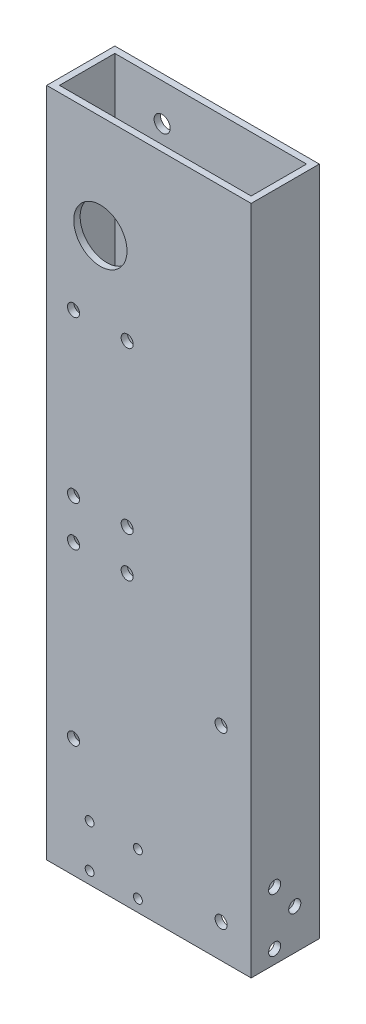
SolidWorks part; units mm, degrees
material "6063-T5"
ref_plane "Front Plane" through (0, 0, 0) normal (0, 0, 1) x (1, 0, 0)
ref_plane "Top Plane" through (0, 0, 0) normal (0, 1, 0) x (1, 0, 0)
ref_plane "Right Plane" through (0, 0, 0) normal (1, 0, 0) x (0, 0, -1)
sketch "Sketch1" plane through (0, 0, 0) normal (0, 1, 0) x (1, 0, 0)
  line L1 (-76.2, 25.4) -> (76.2, 25.4)
  line L2 (-76.2, 25.4) -> (-76.2, -25.4)
  line L3 (-76.2, -25.4) -> (76.2, -25.4)
  line L4 (76.2, 25.4) -> (76.2, -25.4)
  line L5 (-76.2, 25.4) -> (76.2, -25.4) construction
  line L6 (-76.2, -25.4) -> (76.2, 25.4) construction
  point P0 (0, 0)
  dimension "D1" = 152.4
  dimension "D2" = 50.8
extrude "Extrude-Thin1" add sketch "Sketch1" along normal blind 500 thin thin type one direction reverse wall 4.7625
hole_wizard "M8 Clearance Hole1" positions "Sketch3" profile "Sketch4" hole size "M8" standard "ANSI Metric" end condition through all
sketch "Sketch3" plane through (0, 0, 25.4) normal (0, 0, 1) x (1, 0, 0)
  line L0 (-76.2, 225) -> (3.8, 225)
  line L1 (-76.2, 500) -> (-76.2, 0) construction
  line L3 (-76.2, 0) -> (76.2, 0) construction
  line L4 (3.8, 225) -> (3.8, 385)
  line L5 (3.8, 385) -> (-76.2, 385)
  line L6 (-76.2, 385) -> (-76.2, 225)
  line L8 (-56.2, 215) -> (-16.2, 215)
  line L11 (-56.2, 215) -> (-56.2, 151.6667)
  line L12 (-56.2, 151.6667) -> (-56.2, 88.3333)
  line L13 (-56.2, 88.3333) -> (-56.2, 25)
  line L15 (-36.2, 215) -> (-36.2, 225)
  line L17 (-56.2, 25) -> (53.8, 25)
  line L18 (53.8, 25) -> (53.8, 151.6667)
  line L19 (53.8, 151.6667) -> (-56.2, 151.6667)
  line L22 (-56.2, 88.3333) -> (-76.2, 88.3333)
  line L27 (-36.2, 423) -> (-36.2, 385)
  circle A0 centre (-36.2, 423) radius 49.2125
  point P18 (-56.2, 215)
  point P19 (-16.2, 215)
  point P26 (-56.2, 88.3333)
  point P35 (53.8, 25)
  point P36 (53.8, 151.6667)
  dimension "D9" = 98.425
  dimension "D1" = 200
  dimension "D2" = 80
  dimension "D3" = 160
  dimension "D4" = 25
  dimension "D5" = 10
  dimension "D6" = 40
  dimension "D7" = 110
  dimension "D8" = 38
sketch "Sketch4" plane through (53.8, 151.6667, 25.4) normal (1, 0, 0) x (0, -1, 0)
  line L0 (0, 0) -> (0, 50.8)
  line L1 (0, 50.8) -> (4.5, 50.8)
  line L2 (4.5, 50.8) -> (4.5, 0)
  line L5 (4.5, 0) -> (0, 0)
  line L11 (0, -6.35) -> (0, 107.95) construction
  dimension "Thru Hole Dia." = 9
  dimension "Thru Hole Depth" = 50.8
hole_wizard "M8 Clearance Hole2" positions "Sketch5" profile "Sketch6" hole size "M8" standard "ANSI Metric" end condition through all
sketch "Sketch5" plane through (0, 0, 25.4) normal (0, 0, 1) x (1, 0, 0)
  line L1 (-56.2, 365) -> (-16.2, 365)
  line L2 (-56.2, 365) -> (-56.2, 245)
  line L3 (-56.2, 245) -> (-16.2, 245)
  line L4 (-16.2, 365) -> (-16.2, 245)
  line L5 (-56.2, 215) -> (-16.2, 215) construction
  line L6 (-36.2, 225) -> (-36.2, 245)
  line L7 (-76.2, 225) -> (3.8, 225) construction
  point P1 (-56.2, 365)
  point P2 (-16.2, 245)
  point P153 (-56.2, 245)
  point P154 (-16.2, 365)
  dimension "D1" = 20
  dimension "D2" = 120
sketch "Sketch6" plane through (-56.2, 365, 25.4) normal (1, 0, 0) x (0, -1, 0)
  line L0 (0, 0) -> (0, 50.8)
  line L1 (0, 50.8) -> (4.5, 50.8)
  line L2 (4.5, 50.8) -> (4.5, 0)
  line L5 (4.5, 0) -> (0, 0)
  line L11 (0, -6.35) -> (0, 107.95) construction
  dimension "Thru Hole Dia." = 9
  dimension "Thru Hole Depth" = 50.8
hole_wizard "Ø12.0 (12) Diameter Hole1" positions "Sketch7" profile "Sketch8" hole size "Ø12.0" standard "ANSI Metric" end condition up to next
sketch "Sketch7" plane through (0, 0, -25.4) normal (0, 0, -1) x (-1, 0, 0)
  line L0 (-13.0125, 423) -> (36.2, 373.7875)
  line L3 (-13.0125, 423) -> (36.2, 472.2125)
  line L4 (36.2, 472.2125) -> (85.4125, 423)
  line L5 (85.4125, 423) -> (36.2, 373.7875)
  line L7 (36.2, 423) -> (36.2, 385) construction
  circle A0 centre (36.2, 423) radius 49.2125 construction
  point P0 (36.2, 373.7875)
  point P4 (-13.0125, 423)
  point P6 (36.2, 472.2125)
  point P23 (85.4125, 423)
sketch "Sketch8" plane through (-36.2, 373.7875, -25.4) normal (1, 0, 0) x (0, 1, 0)
  line L0 (0, 0) -> (0, 4.7625)
  line L1 (0, 4.7625) -> (6, 4.7625)
  line L2 (6, 4.7625) -> (6, 0)
  line L5 (6, 0) -> (0, 0)
  line L11 (0, -6.35) -> (0, 107.95) construction
  dimension "Thru Hole Dia." = 12
  dimension "Thru Hole Depth" = 4.7625
sketch "Sketch9" plane through (0, 0, 0) normal (0, 0, 1) x (1, 0, 0)
  circle A0 centre (-36.2, 423) radius 19.8438
  dimension "D1" = 39.6875
extrude "Cut-Extrude1" cut sketch "Sketch9" against normal through all and the other way through all
hole_wizard "M6 Clearance Hole1" positions "Sketch10" profile "Sketch11" hole size "M6" standard "ANSI Metric" end condition through all
sketch "Sketch10" plane through (0, 0, 25.4) normal (0, 0, 1) x (1, 0, 0)
  line L1 (-8.2, 41) -> (-44.2, 41)
  line L2 (-8.2, 41) -> (-8.2, 9)
  line L3 (-8.2, 9) -> (-44.2, 9)
  line L4 (-44.2, 41) -> (-44.2, 9)
  line L5 (-8.2, 41) -> (-44.2, 9) construction
  line L6 (-8.2, 9) -> (-44.2, 41) construction
  line L8 (-56.2, 25) -> (53.8, 25) construction
  line L9 (-76.2, 500) -> (-76.2, 0) construction
  point P2 (-44.2, 9)
  point P107 (-8.2, 41)
  point P108 (-8.2, 9)
  point P109 (-44.2, 41)
  point P114 (-26.2, 25)
  dimension "D1" = 36
  dimension "D2" = 32
  dimension "D3" = 50
sketch "Sketch11" plane through (-44.2, 9, 25.4) normal (1, 0, 0) x (0, -1, 0)
  line L0 (0, 0) -> (0, 50.8)
  line L1 (0, 50.8) -> (3.3, 50.8)
  line L2 (3.3, 50.8) -> (3.3, 0)
  line L5 (3.3, 0) -> (0, 0)
  line L11 (0, -6.35) -> (0, 107.95) construction
  dimension "Thru Hole Dia." = 6.6
  dimension "Thru Hole Depth" = 50.8
hole_wizard "M8 Clearance Hole3" positions "Sketch12" profile "Sketch14" hole size "M8" standard "ANSI Metric" end condition up to next
sketch "Sketch12" plane through (76.2, 0, 0) normal (1, 0, 0) x (0, 0, -1)
  line L1 (-7.9, 50) -> (7.1, 50)
  line L2 (-7.9, 50) -> (-7.9, 10)
  line L3 (-7.9, 10) -> (7.1, 10)
  line L4 (7.1, 50) -> (7.1, 10)
  line L5 (-25.4, 0) -> (25.4, 0) construction
  line L6 (-25.4, 88.3333) -> (-25.4, 25) construction
  point P1 (-7.9, 50)
  point P87 (-7.9, 10)
  point P98 (7.1, 30)
  dimension "D1" = 10
  dimension "D2" = 17.5
  dimension "D3" = 15
  dimension "D4" = 40
sketch "Sketch14" plane through (76.2, 50, 7.9) normal (0, 1, 0) x (0, 0, -1)
  line L0 (0, 0) -> (0, 4.7625)
  line L1 (0, 4.7625) -> (4.5, 4.7625)
  line L2 (4.5, 4.7625) -> (4.5, 0)
  line L5 (4.5, 0) -> (0, 0)
  line L11 (0, -6.35) -> (0, 107.95) construction
  dimension "Thru Hole Dia." = 9
  dimension "Thru Hole Depth" = 4.7625
hole_wizard "Ø16.0 (16) Diameter Hole1" positions "Sketch15" profile "Sketch16" hole size "Ø16.0" standard "ANSI Metric" end condition up to next
sketch "Sketch15" plane through (-76.2, 0, 0) normal (-1, 0, 0) x (0, 0, 1)
  line L0 (-7.1, 50) -> (7.9, 10)
  point P0 (0.4, 30)
  point P9 (0.4, 30)
sketch "Sketch16" plane through (-76.2, 30, 0.4) normal (0, 1, 0) x (0, 0, 1)
  line L0 (0, 0) -> (0, 4.7625)
  line L1 (0, 4.7625) -> (8, 4.7625)
  line L2 (8, 4.7625) -> (8, 0)
  line L5 (8, 0) -> (0, 0)
  line L11 (0, -6.35) -> (0, 107.95) construction
  dimension "Thru Hole Dia." = 16
  dimension "Thru Hole Depth" = 4.7625
